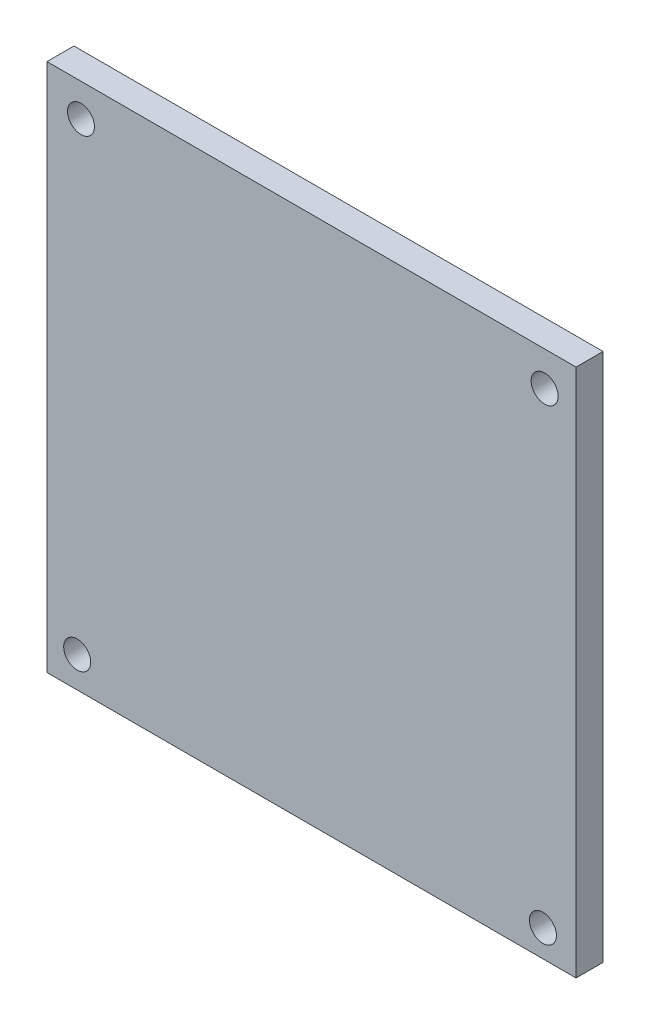
SolidWorks part; units mm, degrees
ref_plane "Front Plane" through (0, 0, 0) normal (0, 0, 1) x (1, 0, 0)
ref_plane "Top Plane" through (0, 0, 0) normal (0, 1, 0) x (1, 0, 0)
ref_plane "Right Plane" through (0, 0, 0) normal (1, 0, 0) x (0, 0, -1)
sketch "Sketch1" plane through (0, 0, 0) normal (0, 0, 1) x (1, 0, 0)
  line L1 (24.892, 24.892) -> (-24.892, 24.892)
  line L2 (24.892, 24.892) -> (24.892, -24.892)
  line L3 (24.892, -24.892) -> (-24.892, -24.892)
  line L4 (-24.892, 24.892) -> (-24.892, -24.892)
  line L5 (24.892, 24.892) -> (-24.892, -24.892) construction
  line L6 (24.892, -24.892) -> (-24.892, 24.892) construction
  point P0 (0, 0)
  dimension "D1" = 49.784
  dimension "D2" = 49.784
extrude "Boss-Extrude1" add sketch "Sketch1" along normal blind 2.54
sketch "Sketch2" plane through (0, 0, 2.54) normal (0, 0, 1) x (1, 0, 0)
  line L4 (-24.892, 24.892) -> (-24.892, -24.892)
  line L5 (-24.892, -24.892) -> (24.892, -24.892)
  line L6 (24.892, -24.892) -> (24.892, 24.892)
  line L7 (24.892, 24.892) -> (-24.892, 24.892)
  line L8 (-24.892, 24.892) -> (-24.892, -24.892)
  line L9 (-24.892, -24.892) -> (24.892, -24.892)
  line L10 (24.892, -24.892) -> (24.892, 24.892)
  line L11 (24.892, 24.892) -> (-24.892, 24.892)
  circle A0 centre (-22.0472, -22.0037) radius 1.27 construction
  circle A1 centre (-22.0472, -22.0037) radius 1.27
  circle A2 centre (-21.6885, 21.8185) radius 1.27 construction
  circle A3 centre (-21.6885, 21.8185) radius 1.27
  circle A4 centre (21.775, -22.3624) radius 1.27 construction
  circle A5 centre (21.775, -22.3624) radius 1.27
  circle A6 centre (21.9345, 21.6613) radius 1.27 construction
  circle A7 centre (21.9345, 21.6613) radius 1.27
  dimension "D1" = 0
extrude "Cut-Extrude1" cut sketch "Sketch2" against normal through all contours A3 | A1 | A5 | A7 region at (-22.0472, -22.0037, 2.54) region at (-21.6885, 21.8185, 2.54) region at (21.775, -22.3624, 2.54) region at (21.9345, 21.6613, 2.54)
